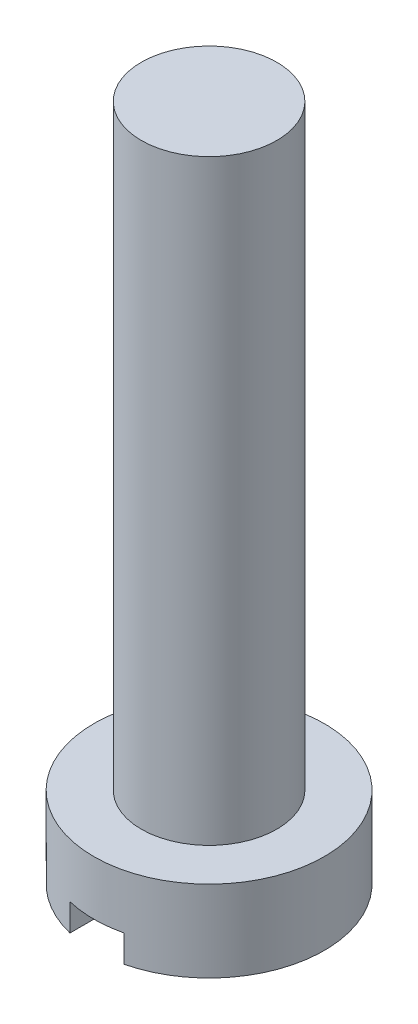
SolidWorks part; units mm, degrees
ref_plane "Plan de face" through (0, 0, 0) normal (0, 0, 1) x (1, 0, 0)
ref_plane "Plan de dessus" through (0, 0, 0) normal (0, 1, 0) x (1, 0, 0)
ref_plane "Plan de droite" through (0, 0, 0) normal (1, 0, 0) x (0, 0, -1)
sketch "Esquisse1" plane through (0, 0, 0) normal (0, 1, 0) x (1, 0, 0)
  circle A0 centre (0, 0) radius 2.5
  circle A1 centre (0, 0) radius 4.25
extrude "Boss.-Extru.1" add sketch "Esquisse1" along normal blind 3
extrude "Boss.-Extru.3" add sketch "Esquisse1<4>" along normal blind 25 contours A0
sketch "Esquisse1<4>" plane through (0, 0, 0) normal (0, 1, 0) x (1, 0, 0) same geometry as "Esquisse1"
sketch "Esquisse2" plane through (0, 0, 0) normal (0, -1, 0) x (1, 0, 0)
  line L0 (0, 0) -> (1, 0) construction
  line L1 (0, 0) -> (-1, 0) construction
  line L2 (-1, 0) -> (-1, 8)
  line L3 (-1, 8) -> (1, 8)
  line L4 (1, 8) -> (1, -8)
  line L5 (1, -8) -> (-1, -8)
  line L6 (-1, -8) -> (-1, 0)
extrude "Enlèv. mat.-Extru.1" cut sketch "Esquisse2" against normal blind 1
